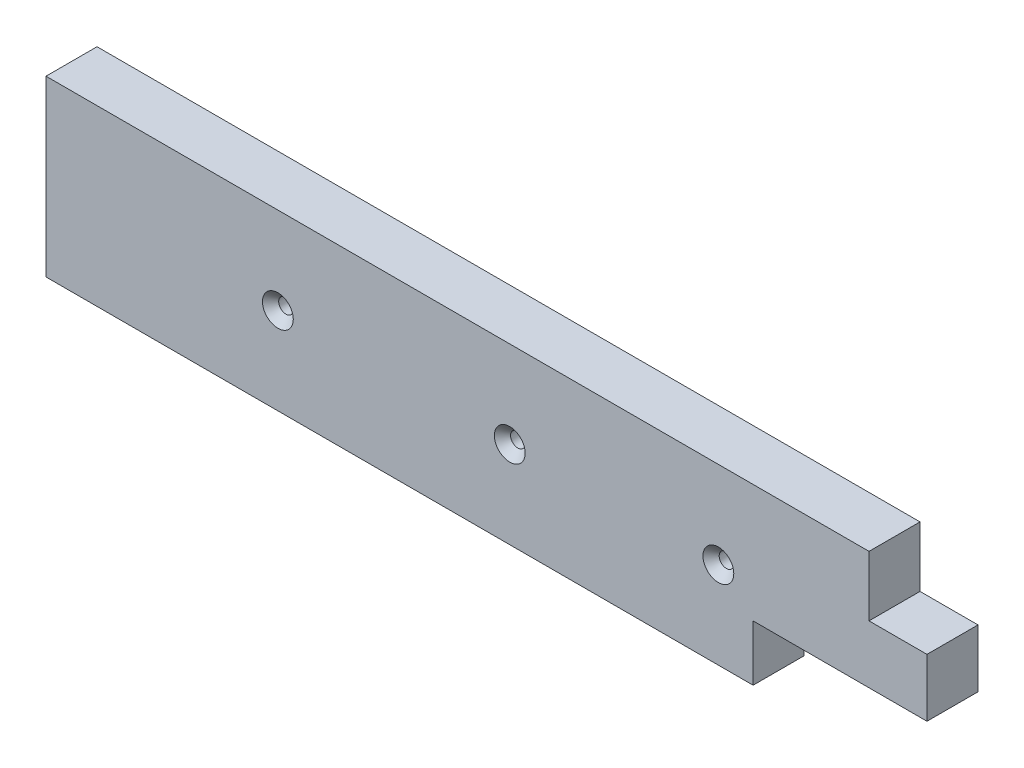
SolidWorks part; units mm, degrees
ref_plane "Front Plane" through (0, 0, 0) normal (0, 0, 1) x (1, 0, 0)
ref_plane "Top Plane" through (0, 0, 0) normal (0, 1, 0) x (1, 0, 0)
ref_plane "Right Plane" through (0, 0, 0) normal (1, 0, 0) x (0, 0, -1)
sketch "Sketch1" plane through (0, 0, 0) normal (0, 1, 0) x (1, 0, 0)
  line L1 (-193.0064, -11.176) -> (193.0064, -11.176)
  line L2 (-193.0064, -11.176) -> (-193.0064, 11.176)
  line L3 (-193.0064, 11.176) -> (193.0064, 11.176)
  line L4 (193.0064, -11.176) -> (193.0064, 11.176)
  line L5 (-193.0064, -11.176) -> (193.0064, 11.176) construction
  line L6 (-193.0064, 11.176) -> (193.0064, -11.176) construction
  point P0 (0, 0)
extrude "Boss-Extrude1" add sketch "Sketch1" along normal mid plane 76.2 contours L1 L4 L3 L2
sketch "Sketch3" plane through (0, 0, 11.176) normal (0, 0, 1) x (1, 0, 0)
  line L1 (167.6064, 11.7146) -> (193.0064, 11.7146)
  line L2 (193.0064, 38.1) -> (193.0064, 11.7146)
  line L3 (167.6064, 11.7146) -> (167.6064, 38.1)
  line L4 (167.6064, 38.1) -> (193.0064, 38.1)
  line L5 (116.8199, -13.6854) -> (193.0064, -13.6854)
  line L6 (116.8199, -13.6854) -> (116.8199, -38.1)
  line L7 (116.8199, -38.1) -> (193.0064, -38.1)
  line L8 (193.0064, -13.6854) -> (193.0064, -38.1)
hole_wizard "CSK for M6 Hex Socket Countersunk Head Screw6" positions "Sketch21" profile "Sketch20" countersink size "M6" standard "Lanco STD" end condition through all
sketch "Sketch21" plane through (0, 0, 11.176) normal (0, 0, 1) x (1, 0, 0)
  line L0 (-193.0064, 38.1) -> (-193.0064, -38.1) construction
  point P0 (-91.4064, 0)
  point P3 (-193.0064, 0)
  dimension "D1" = 101.6
sketch "Sketch20" plane through (-91.4064, 0, 11.176) normal (1, 0, 0) x (0, -1, 0)
  line L0 (0, 0) -> (0, 22.352)
  line L1 (0, 22.352) -> (3.2, 22.352)
  line L2 (3.2, 22.352) -> (3.2, 3.55)
  line L3 (3.2, 3.55) -> (6.75, 0)
  line L5 (6.75, 0) -> (0, 0)
  line L6 (-3.2, 3.55) -> (-6.75, 0) construction
  line L11 (0, -6.35) -> (0, 107.95) construction
  dimension "Thru Hole Dia." = 6.4
  dimension "Thru Hole Depth" = 22.352
  dimension "Near C'Sink Dia." = 13.5
  dimension "Near C'Sink Angle" = 90
hole_wizard "CSK for M6 Hex Socket Countersunk Head Screw7" positions "Sketch23" profile "Sketch22" countersink size "M6" standard "Lanco STD" end condition through all
sketch "Sketch23" plane through (0, 0, 11.176) normal (0, 0, 1) x (1, 0, 0)
  line L1 (-193.0064, 38.1) -> (-193.0064, -38.1) construction
  point P0 (10.1936, 0)
  point P5 (-193.0064, 0)
  dimension "D1" = 203.2
sketch "Sketch22" plane through (10.1936, 0, 11.176) normal (1, 0, 0) x (0, -1, 0)
  line L0 (0, 0) -> (0, 22.352)
  line L1 (0, 22.352) -> (3.2, 22.352)
  line L2 (3.2, 22.352) -> (3.2, 3.55)
  line L3 (3.2, 3.55) -> (6.75, 0)
  line L5 (6.75, 0) -> (0, 0)
  line L6 (-3.2, 3.55) -> (-6.75, 0) construction
  line L11 (0, -6.35) -> (0, 107.95) construction
  dimension "Thru Hole Dia." = 6.4
  dimension "Thru Hole Depth" = 22.352
  dimension "Near C'Sink Dia." = 13.5
  dimension "Near C'Sink Angle" = 90
hole_wizard "CSK for M6 Hex Socket Countersunk Head Screw8" positions "Sketch25" profile "Sketch24" countersink size "M6" standard "Lanco STD" end condition through all
sketch "Sketch25" plane through (0, 0, 11.176) normal (0, 0, 1) x (1, 0, 0)
  point P0 (101.6, 0)
  dimension "D1" = 101.6
sketch "Sketch24" plane through (101.6, 0, 11.176) normal (1, 0, 0) x (0, -1, 0)
  line L0 (0, 0) -> (0, 22.352)
  line L1 (0, 22.352) -> (3.2, 22.352)
  line L2 (3.2, 22.352) -> (3.2, 3.55)
  line L3 (3.2, 3.55) -> (6.75, 0)
  line L5 (6.75, 0) -> (0, 0)
  line L6 (-3.2, 3.55) -> (-6.75, 0) construction
  line L11 (0, -6.35) -> (0, 107.95) construction
  dimension "Thru Hole Dia." = 6.4
  dimension "Thru Hole Depth" = 22.352
  dimension "Near C'Sink Dia." = 13.5
  dimension "Near C'Sink Angle" = 90
extrude "Cut-Extrude1" cut sketch "Sketch3" against normal through all
